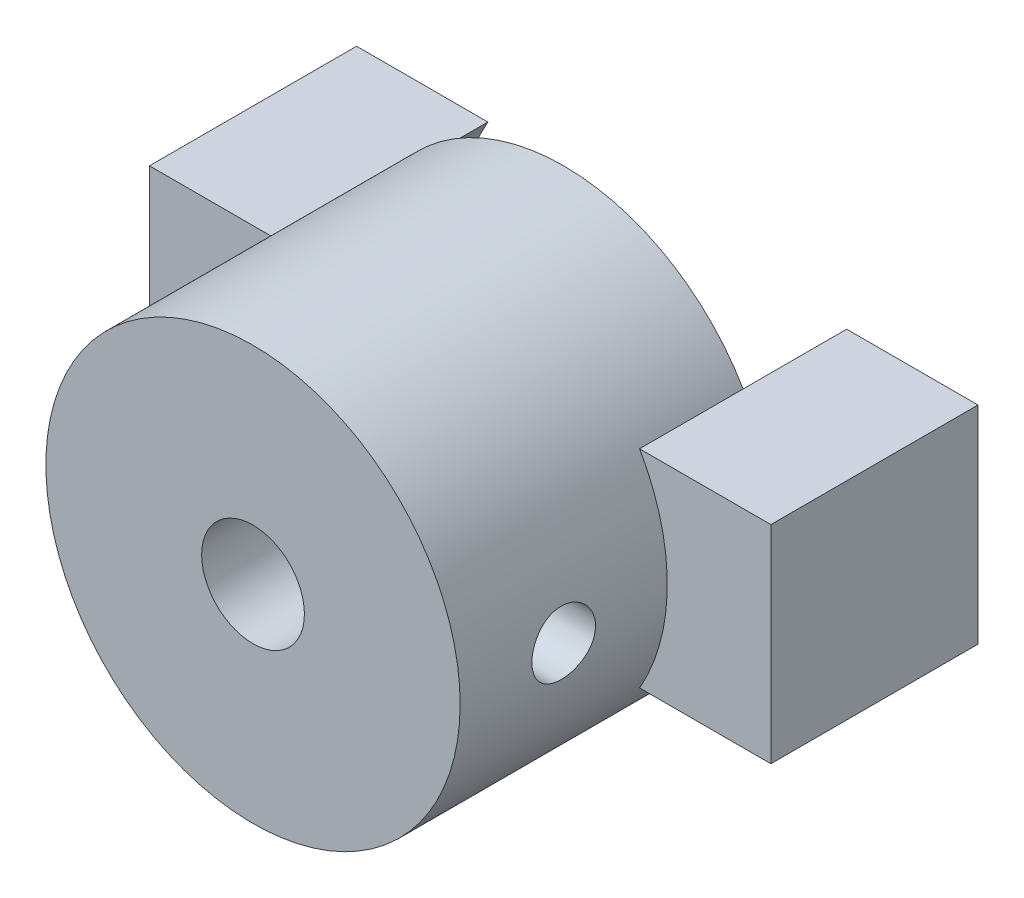
SolidWorks part; units mm, degrees
material "PLA"
ref_plane "Front Plane" through (0, 0, 0) normal (0, 0, 1) x (1, 0, 0)
ref_plane "Top Plane" through (0, 0, 0) normal (0, 1, 0) x (1, 0, 0)
ref_plane "Right Plane" through (0, 0, 0) normal (1, 0, 0) x (0, 0, -1)
sketch "Sketch1" plane through (0, 0, 0) normal (0, 0, 1) x (1, 0, 0)
  circle A0 centre (0, 0) radius 12.7
  circle A1 centre (0, 0) radius 3.15
  dimension "D1" = 25.4
  dimension "D2" = 6.3
extrude "Boss-Extrude1" add sketch "Sketch1" along normal blind 12.7
ref_plane "Plane1" through (25.4, 0, 0) normal (1, 0, 0) x (0, 0, -1)
sketch "Sketch2" plane through (25.4, 0, 0) normal (1, 0, 0) x (0, 0, -1)
  line L0 (0, -12.7) -> (0, 12.7) construction
  line L1 (-12.7, 12.7) -> (-12.7, -12.7) construction
  line L2 (0, -12.7) -> (0, 12.7)
  line L3 (-12.7, 12.7) -> (-12.7, -12.7)
  line L4 (-12.7, 0) -> (0, 0) construction
  circle A0 centre (-6.35, 0) radius 1.95
  dimension "D1" = 3.9
extrude "Cut-Extrude1" cut sketch "Sketch2" against normal up to surface (22.25 mm away) contours L4 A0 | A0 L4 region at (25.4, 0.8276, 6.35) region at (25.4, -0.8276, 6.35) up to face at (3.15, 0, 12.7)
sketch "Sketch3" plane through (0, 0, 0) normal (0, 0, -1) x (-1, 0, 0)
  line L1 (-19.05, -6.35) -> (19.05, -6.35)
  line L2 (-19.05, -6.35) -> (-19.05, 6.35)
  line L3 (-19.05, 6.35) -> (19.05, 6.35)
  line L4 (19.05, -6.35) -> (19.05, 6.35)
  line L5 (-19.05, -6.35) -> (19.05, 6.35) construction
  line L6 (-19.05, 6.35) -> (19.05, -6.35) construction
  circle A1 centre (0, 0) radius 12.7
  circle A2 centre (0, 0) radius 12.7
  circle M2 centre (0, 0) radius 12.7
  circle M3 centre (0, 0) radius 3.15
  dimension "D2" = 12.7
  dimension "D3" = 38.1
  dimension "D1" = 0
extrude "Boss-Extrude2" add sketch "Sketch3" along normal blind 6.35 contours L3 L1 M2 M3 | L3 L2 L1 M2 | L1 L4 L3 M2 | L3 M2 | L1 M2 region at (15.5812, 0, 0) region at (12.416, 0, 0) region at (0, -8.9538, 0) region at (-15.5812, 0, 0) region at (0, 8.9538, 0)
extrude "Boss-Extrude3" add sketch "Sketch3<3>" along normal blind 6.35 from surface contours L3 L2 L1 M2 | L1 L4 L3 M2 region at (15.5812, 0, 0) region at (-15.5812, 0, 0) starting at face at (0, 0, -6.35)
sketch "Sketch3<3>" plane through (0, 0, 0) normal (0, 0, -1) x (-1, 0, 0) same geometry as "Sketch3"
